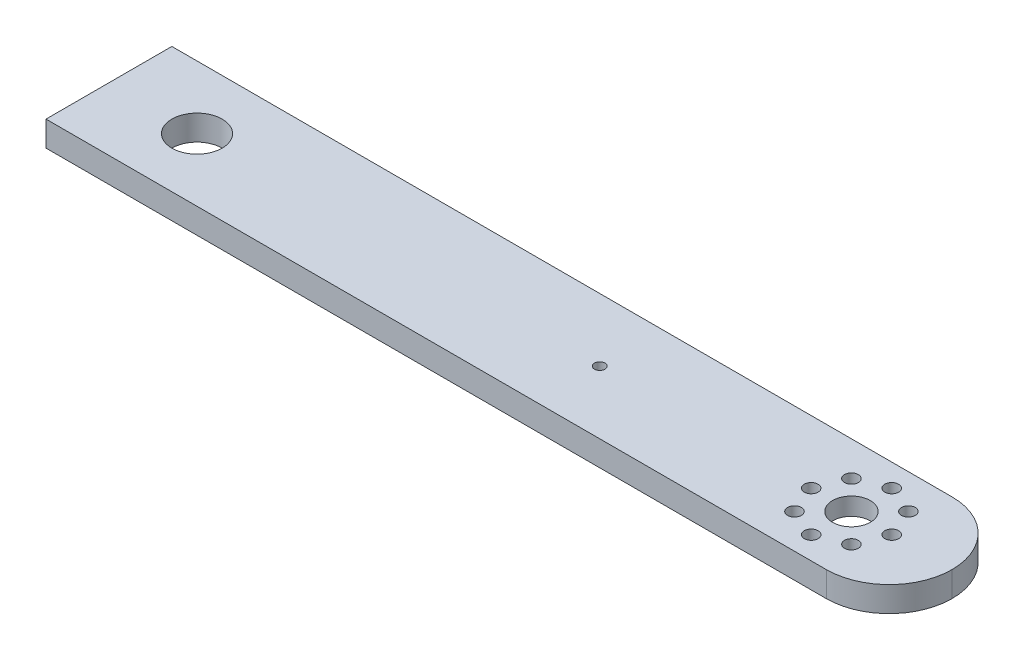
SolidWorks part; units mm, degrees
material "3.0255 (EN-AW 1350A)"
ref_plane "Piano frontale" through (0, 0, 0) normal (0, 0, 1) x (1, 0, 0)
ref_plane "Piano superiore" through (0, 0, 0) normal (0, 1, 0) x (1, 0, 0)
ref_plane "Piano destro" through (0, 0, 0) normal (1, 0, 0) x (0, 0, -1)
sketch "Schizzo1" plane through (0, 0, 0) normal (0, 1, 0) x (1, 0, 0)
  line L0 (0, 0) -> (40, 0) construction
  line L1 (-295, 25) -> (40, 25)
  line L2 (-295, 25) -> (-295, -25)
  line L3 (-295, -25) -> (40, -25)
  line L4 (40, 25) -> (40, -25)
  line L5 (-260, 0) -> (0, 0) construction
  circle A0 centre (0, 0) radius 7.5
  circle A1 centre (-260, 0) radius 10
  point P8 (40, 0)
  dimension "D2" = 20
  dimension "D3" = 15
  dimension "D1" = 260
  dimension "D4" = 50
  dimension "D5" = 35
  dimension "D6" = 40
extrude "Estrusione-Estrusione1" add sketch "Schizzo1" along normal mid plane 10
sketch "Schizzo2" plane through (0, 5, 0) normal (0, 1, 0) x (1, 0, 0)
  circle A0 centre (0, 0) radius 16 construction
  circle A1 centre (-16, 0) radius 2.75
  dimension "D1" = 32
  dimension "D2" = 5.5
extrude "Taglio-Estrusione1" cut sketch "Schizzo2" against normal through all
pattern_circular "RipetizioneCircolare1" count 8 over 360 about axis through (0, 5, 0) along (0, -1, 0) of "Taglio-Estrusione1"
fillet "Raccordo1" radius 25 2 edges at (40, 0, 25) (40, 0, -25)
sketch "Schizzo3" plane through (0, 5, 0) normal (0, 1, 0) x (1, 0, 0)
  line L0 (0, 0) -> (-100, 0) construction
  circle A0 centre (-100, 0) radius 2.1
  dimension "D2" = 4.2
  dimension "D1" = 100
extrude "Taglio-Estrusione2" cut sketch "Schizzo3" against normal through all
sketch "Schizzo4" plane through (0, -5, 0) normal (0, -1, 0) x (1, 0, 0)
  circle A0 centre (0, 0) radius 21
  dimension "D1" = 42
extrude "Taglio-Estrusione3" cut sketch "Schizzo4" against normal blind 3
chamfer "Smusso1" distance 0.5 angle 45 1 edges at (0, -5, -21)
sketch "Schizzo5" plane through (0, -5, 0) normal (0, -1, 0) x (1, 0, 0)
  line L43 (-244, 9.0635) -> (-244, 1.5)
  line L44 (-260, 11.575) -> (-245.4156, 11.575)
  line L45 (-250, -11.575) -> (-260, -11.575)
  line L46 (-250, -14.5) -> (-250, -11.575)
  line L47 (-252, -15) -> (-250.5, -15)
  line L48 (-252.5, -13) -> (-252.5, -14.5)
  line L49 (-255, -12.5) -> (-253, -12.5)
  line L50 (-255.5, -14.5) -> (-255.5, -13)
  line L51 (-264.5, -15) -> (-256, -15)
  line L52 (-265, -13) -> (-265, -14.5)
  line L53 (-267.5, -12.5) -> (-265.5, -12.5)
  line L54 (-268, -14.5) -> (-268, -13)
  line L55 (-270.6, -15) -> (-268.5, -15)
  line L56 (-271.1, -12.8) -> (-271.1, -14.5)
  line L57 (-269.75, -12.8) -> (-271.1, -12.8)
  line L58 (-269.75, -10) -> (-269.75, -12.8)
  line L59 (-271, -10) -> (-269.75, -10)
  line L60 (-271, -8.5) -> (-271, -10)
  line L61 (-275.5, -8) -> (-271.5, -8)
  line L62 (-276, -10) -> (-276, -8.5)
  line L63 (-277.25, -10) -> (-276, -10)
  line L64 (-277.25, -12.8) -> (-277.25, -10)
  line L65 (-275.9, -12.8) -> (-277.25, -12.8)
  line L66 (-275.9, -14.5) -> (-275.9, -12.8)
  line L67 (-279.3, -15) -> (-276.4, -15)
  line L68 (-279.8, -11.5) -> (-279.8, -14.5)
  line L69 (-282.3, -11) -> (-280.3, -11)
  line L70 (-282.8, -14.5) -> (-282.8, -11.5)
  line L71 (-284, -15) -> (-283.3, -15)
  line L72 (-285, -4.6) -> (-285, -14)
  line L73 (-282.8, -4.1) -> (-284.5, -4.1)
  line L74 (-282.8, -8.25) -> (-282.8, -4.1)
  line L75 (-279.5, -8.25) -> (-282.8, -8.25)
  line L76 (-276, -4) -> (-279.5, -8.25)
  line L77 (-276, 4) -> (-276, -4)
  line L78 (-279.5, 8.25) -> (-276, 4)
  line L79 (-282.8, 8.25) -> (-279.5, 8.25)
  line L80 (-282.8, 4.1) -> (-282.8, 8.25)
  line L81 (-284.5, 4.1) -> (-282.8, 4.1)
  line L82 (-285, 14) -> (-285, 4.6)
  line L83 (-231, 15) -> (-284, 15)
  line L84 (-230, 2) -> (-230, 14)
  line L85 (-244, 1.5) -> (-230.5, 1.5)
  line L86 (-244, 9.0635) -> (-244, 1.5)
  line L87 (-260, 11.575) -> (-245.4156, 11.575)
  line L88 (-250, -11.575) -> (-260, -11.575)
  line L89 (-250, -14.5) -> (-250, -11.575)
  line L90 (-252, -15) -> (-250.5, -15)
  line L91 (-252.5, -13) -> (-252.5, -14.5)
  line L92 (-255, -12.5) -> (-253, -12.5)
  line L93 (-255.5, -14.5) -> (-255.5, -13)
  line L94 (-264.5, -15) -> (-256, -15)
  line L95 (-265, -13) -> (-265, -14.5)
  line L96 (-267.5, -12.5) -> (-265.5, -12.5)
  line L97 (-268, -14.5) -> (-268, -13)
  line L98 (-270.6, -15) -> (-268.5, -15)
  line L99 (-271.1, -12.8) -> (-271.1, -14.5)
  line L100 (-269.75, -12.8) -> (-271.1, -12.8)
  line L101 (-269.75, -10) -> (-269.75, -12.8)
  line L102 (-271, -10) -> (-269.75, -10)
  line L103 (-271, -8.5) -> (-271, -10)
  line L104 (-275.5, -8) -> (-271.5, -8)
  line L105 (-276, -10) -> (-276, -8.5)
  line L106 (-277.25, -10) -> (-276, -10)
  line L107 (-277.25, -12.8) -> (-277.25, -10)
  line L108 (-275.9, -12.8) -> (-277.25, -12.8)
  line L109 (-275.9, -14.5) -> (-275.9, -12.8)
  line L110 (-279.3, -15) -> (-276.4, -15)
  line L111 (-279.8, -11.5) -> (-279.8, -14.5)
  line L112 (-282.3, -11) -> (-280.3, -11)
  line L113 (-282.8, -14.5) -> (-282.8, -11.5)
  line L114 (-284, -15) -> (-283.3, -15)
  line L115 (-285, -4.6) -> (-285, -14)
  line L116 (-282.8, -4.1) -> (-284.5, -4.1)
  line L117 (-282.8, -8.25) -> (-282.8, -4.1)
  line L118 (-279.5, -8.25) -> (-282.8, -8.25)
  line L119 (-276, -4) -> (-279.5, -8.25)
  line L120 (-276, 4) -> (-276, -4)
  line L121 (-279.5, 8.25) -> (-276, 4)
  line L122 (-282.8, 8.25) -> (-279.5, 8.25)
  line L123 (-282.8, 4.1) -> (-282.8, 8.25)
  line L124 (-284.5, 4.1) -> (-282.8, 4.1)
  line L125 (-285, 14) -> (-285, 4.6)
  line L126 (-231, 15) -> (-284, 15)
  line L127 (-230, 2) -> (-230, 14)
  line L128 (-244, 1.5) -> (-230.5, 1.5)
  arc A26 (-244, 9.0635) -> (-241.5, 11) centre (-243.5, 11) ccw
  arc A27 (-241.5, 11) -> (-245.4156, 11.575) centre (-243.5, 11) ccw
  arc A28 (-260, 11.575) -> (-260, -11.575) centre (-260, 0) ccw
  arc A29 (-250.5, -15) -> (-250, -14.5) centre (-250.5, -14.5) ccw
  arc A30 (-252.5, -14.5) -> (-252, -15) centre (-252, -14.5) ccw
  arc A31 (-252.5, -13) -> (-253, -12.5) centre (-253, -13) ccw
  arc A32 (-255, -12.5) -> (-255.5, -13) centre (-255, -13) ccw
  arc A33 (-256, -15) -> (-255.5, -14.5) centre (-256, -14.5) ccw
  arc A34 (-265, -14.5) -> (-264.5, -15) centre (-264.5, -14.5) ccw
  arc A35 (-265, -13) -> (-265.5, -12.5) centre (-265.5, -13) ccw
  arc A36 (-267.5, -12.5) -> (-268, -13) centre (-267.5, -13) ccw
  arc A37 (-268.5, -15) -> (-268, -14.5) centre (-268.5, -14.5) ccw
  arc A38 (-271.1, -14.5) -> (-270.6, -15) centre (-270.6, -14.5) ccw
  arc A39 (-271, -8.5) -> (-271.5, -8) centre (-271.5, -8.5) ccw
  arc A40 (-275.5, -8) -> (-276, -8.5) centre (-275.5, -8.5) ccw
  arc A41 (-276.4, -15) -> (-275.9, -14.5) centre (-276.4, -14.5) ccw
  arc A42 (-279.8, -14.5) -> (-279.3, -15) centre (-279.3, -14.5) ccw
  arc A43 (-279.8, -11.5) -> (-280.3, -11) centre (-280.3, -11.5) ccw
  arc A44 (-282.3, -11) -> (-282.8, -11.5) centre (-282.3, -11.5) ccw
  arc A45 (-283.3, -15) -> (-282.8, -14.5) centre (-283.3, -14.5) ccw
  arc A46 (-285, -14) -> (-284, -15) centre (-284, -14) ccw
  arc A47 (-284.5, -4.1) -> (-285, -4.6) centre (-284.5, -4.6) ccw
  arc A48 (-285, 4.6) -> (-284.5, 4.1) centre (-284.5, 4.6) ccw
  arc A49 (-284, 15) -> (-285, 14) centre (-284, 14) ccw
  arc A50 (-230, 14) -> (-231, 15) centre (-231, 14) ccw
  arc A51 (-230.5, 1.5) -> (-230, 2) centre (-230.5, 2) ccw
  arc A52 (-244, 9.0635) -> (-241.5, 11) centre (-243.5, 11) ccw
  arc A53 (-241.5, 11) -> (-245.4156, 11.575) centre (-243.5, 11) ccw
  arc A54 (-260, 11.575) -> (-260, -11.575) centre (-260, 0) ccw
  arc A55 (-250.5, -15) -> (-250, -14.5) centre (-250.5, -14.5) ccw
  arc A56 (-252.5, -14.5) -> (-252, -15) centre (-252, -14.5) ccw
  arc A57 (-252.5, -13) -> (-253, -12.5) centre (-253, -13) ccw
  arc A58 (-255, -12.5) -> (-255.5, -13) centre (-255, -13) ccw
  arc A59 (-256, -15) -> (-255.5, -14.5) centre (-256, -14.5) ccw
  arc A60 (-265, -14.5) -> (-264.5, -15) centre (-264.5, -14.5) ccw
  arc A61 (-265, -13) -> (-265.5, -12.5) centre (-265.5, -13) ccw
  arc A62 (-267.5, -12.5) -> (-268, -13) centre (-267.5, -13) ccw
  arc A63 (-268.5, -15) -> (-268, -14.5) centre (-268.5, -14.5) ccw
  arc A64 (-271.1, -14.5) -> (-270.6, -15) centre (-270.6, -14.5) ccw
  arc A65 (-271, -8.5) -> (-271.5, -8) centre (-271.5, -8.5) ccw
  arc A66 (-275.5, -8) -> (-276, -8.5) centre (-275.5, -8.5) ccw
  arc A67 (-276.4, -15) -> (-275.9, -14.5) centre (-276.4, -14.5) ccw
  arc A68 (-279.8, -14.5) -> (-279.3, -15) centre (-279.3, -14.5) ccw
  arc A69 (-279.8, -11.5) -> (-280.3, -11) centre (-280.3, -11.5) ccw
  arc A70 (-282.3, -11) -> (-282.8, -11.5) centre (-282.3, -11.5) ccw
  arc A71 (-283.3, -15) -> (-282.8, -14.5) centre (-283.3, -14.5) ccw
  arc A72 (-285, -14) -> (-284, -15) centre (-284, -14) ccw
  arc A73 (-284.5, -4.1) -> (-285, -4.6) centre (-284.5, -4.6) ccw
  arc A74 (-285, 4.6) -> (-284.5, 4.1) centre (-284.5, 4.6) ccw
  arc A75 (-284, 15) -> (-285, 14) centre (-284, 14) ccw
  arc A76 (-230, 14) -> (-231, 15) centre (-231, 14) ccw
  arc A77 (-230.5, 1.5) -> (-230, 2) centre (-230.5, 2) ccw
  dimension "D1" = 0
